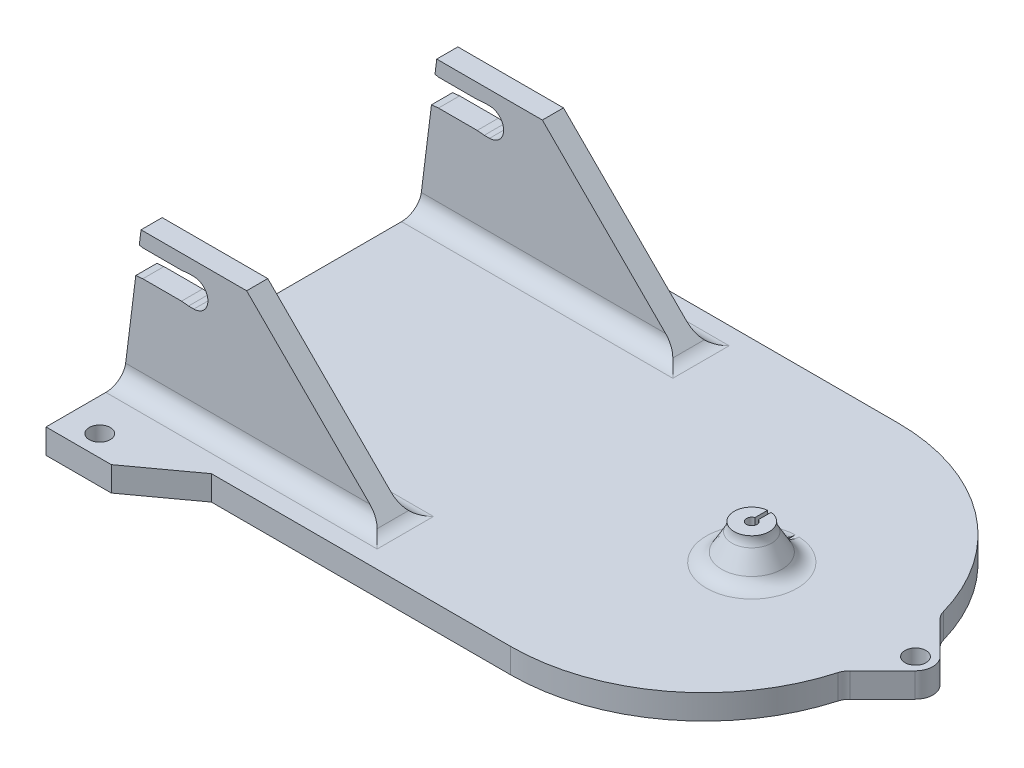
SolidWorks part; units mm, degrees
ref_plane "Front Plane" through (0, 0, 0) normal (0, 0, 1) x (1, 0, 0)
ref_plane "Top Plane" through (0, 0, 0) normal (0, 1, 0) x (1, 0, 0)
ref_plane "Right Plane" through (0, 0, 0) normal (1, 0, 0) x (0, 0, -1)
sketch "Sketch1" plane through (0, 0, 0) normal (0, 1, 0) x (1, 0, 0)
  circle A0 centre (0, 0) radius 55
  dimension "D1" = 110
extrude "Boss-Extrude1" add sketch "Sketch1" along normal blind 7
sketch "Sketch2" plane through (0, 7, 0) normal (0, 1, 0) x (1, 0, 0)
  line L0 (13, 1.4142) -> (13, 4.9749)
  line L1 (14, 1.4142) -> (14, 4.9749)
  line L2 (13, 3.1946) -> (14, 3.1946) construction
  arc A0 (13, 1.4142) -> (14, 1.4142) centre (13.5, 0) ccw
  arc A1 (13, 4.9749) -> (14, 4.9749) centre (13.5, 0) ccw
  circle A2 centre (0, 0) radius 55 construction
  point P10 (13.5, 3.1946)
  dimension "D1" = 3
  dimension "D2" = 10
  dimension "D3" = 13.5
  dimension "D4" = 1
extrude "Boss-Extrude2" add sketch "Sketch2" along normal blind 10
sketch "Sketch3" plane through (0, 7, 0) normal (0, 1, 0) x (1, 0, 0)
  circle A0 centre (0, 0) radius 11
  dimension "D1" = 22
extrude "Cut-Extrude1" [suppressed] cut sketch "Sketch3" against normal through all both
sketch "Sketch4" plane through (0, 7, 0) normal (0, 1, 0) x (1, 0, 0)
  line L0 (0, 55) -> (-120, 55)
  line L1 (-120, 55) -> (-120, -55)
  line L2 (-120, -55) -> (0, -55)
  circle A0 centre (0, 0) radius 55 construction
  arc A1 (0, 55) -> (0, -55) centre (0, 0) ccw
  dimension "D1" = 120
extrude "Boss-Extrude3" add sketch "Sketch4" against normal up to surface (7 mm away) up to face at (0, 0, 55)
sketch "Sketch5" plane through (0, 7, 0) normal (0, 1, 0) x (1, 0, 0)
  line L0 (-120, 0) -> (55, 0) construction
  line L1 (-120, 55) -> (-120, -55) construction
  arc A0 (0, -55) -> (0, 55) centre (0, 0) ccw construction
sketch "Sketch6" plane through (0, 7, 0) normal (0, 1, 0) x (1, 0, 0)
  line L0 (-120, 55) -> (-120, -55) construction
  line L1 (-85, -39) -> (-115, -39)
  line L2 (-85, -39) -> (-85, -45)
  line L3 (-85, -45) -> (-115, -45)
  line L4 (-115, -39) -> (-115, -45)
  line L5 (-120, -55) -> (0, -55) construction
  dimension "D1" = 30
  dimension "D2" = 5
  dimension "D3" = 10
  dimension "D4" = 6
extrude "Boss-Extrude4" add sketch "Sketch6" along normal blind 40
chamfer "Chamfer1" distance 40 angle 45 1 edges at (-85, 7, 42)
sketch "Sketch8" plane through (0, 0, 45) normal (0, 0, 1) x (1, 0, 0)
  line L0 (-115, 47) -> (-120, 7)
  line L1 (-120, 7) -> (55, 7) construction
  line L2 (-120, 7) -> (-115, 7)
  line L3 (-115, 7) -> (-115, 47)
extrude "Boss-Extrude5" add sketch "Sketch8" against normal up to surface (6 mm away) up to face at (-90, 27, 39)
mirror "Mirror1" about plane through (0, 0, 0) normal (0, 0, 1) of "Boss-Extrude4", "Chamfer1", "Boss-Extrude5"
fillet "Fillet1" radius 5 6 edges at (-45, 7, -42) (-45, 7, 42) (-82.5, 7, -45) (-82.5, 7, -39) (-82.5, 7, 39) (-82.5, 7, 45)
chamfer "Chamfer2" distance 5 angle 60 1 edges at (13.5, 7, 5) first distance on face at (13.5, 7, 0.0277)
sketch "Sketch9" plane through (0, 7, 0) normal (0, 1, 0) x (1, 0, 0)
  line L0 (-120, 55) -> (-120, 67)
  line L1 (-120, 67) -> (-101.4622, 67)
  line L2 (-101.4622, 67) -> (-85, 55)
  line L3 (0, 55) -> (-120, 55) construction
  line L4 (-85, 55) -> (-120, 55)
  line L5 (-120, 61) -> (-100.4732, 61) construction
  line L6 (-110.7311, 67) -> (-110.7311, 56.2712) construction
  circle A0 centre (-110.7311, 61) radius 3
  point P14 (-110.2366, 61)
  dimension "D1" = 6
  dimension "D2" = 12
  dimension "D3" = 35
  dimension "D4" = 18.5378
extrude "Boss-Extrude6" add sketch "Sketch9" against normal up to surface (7 mm away) up to face at (-46.25, 0, 0)
mirror "Mirror2" about plane through (0, 0, 0) normal (0, 0, 1) of "Boss-Extrude6"
sketch "Sketch10" plane through (0, 7, 0) normal (0, 1, 0) x (1, 0, 0)
  line L0 (53.2547, 13.7453) -> (67, 0)
  line L1 (67, 0) -> (53.2547, -13.7453)
  circle A0 centre (60, 0) radius 3
  arc A1 (0, -55) -> (0, 55) centre (0, 0) ccw construction
  arc A2 (53.2547, -13.7453) -> (53.2547, 13.7453) centre (0, 0) ccw
  dimension "D1" = 6
  dimension "D2" = 5
  dimension "D3" = 12
extrude "Boss-Extrude7" add sketch "Sketch10" against normal up to surface (7 mm away) up to face at (-69.7406, 0, 0)
fillet "Fillet3" radius 5 3 edges at (53.2547, 3.5, -13.7453) (67, 3.5, 0) (53.2547, 3.5, 13.7453)
fillet "Fillet4" radius 5 2 edges at (13.5, 15.6603, 5) (13.5, 7, 10)
sketch "Sketch11" plane through (0, 0, 45) normal (0, 0, 1) x (1, 0, 0)
  line L0 (-115, 47) -> (-85, 47) construction
  line L1 (-100, 43) -> (-101.5, 43)
  line L2 (-115, 47) -> (-119.375, 12) construction
  line L3 (-100, 35) -> (-101.5, 35)
  line L4 (-115.5, 43) -> (-116.5, 35)
  line L5 (-100, 39) -> (-118.6827, 39) construction
  line L6 (-116.5, 35) -> (-114.5, 35.2)
  line L7 (-114.5, 35.2) -> (-103.5, 35.2)
  line L8 (-103.5, 35.2) -> (-101.5, 35)
  line L9 (-115.5, 43) -> (-114.5, 42.8)
  line L10 (-114.5, 42.8) -> (-103.5, 42.8)
  line L11 (-103.5, 42.8) -> (-101.5, 43)
  arc A1 (-100, 35) -> (-100, 43) centre (-100, 39) ccw
  point P15 (-116, 39)
  dimension "D1" = 8
  dimension "D2" = 20
  dimension "D3" = 8
  dimension "D4" = 2
  dimension "D5" = 2
  dimension "D6" = 11
  dimension "D7" = 0.2
  dimension "D8" = 1.5
  dimension "D9" = 0.2
  dimension "D10" = 1
extrude "Cut-Extrude3" cut sketch "Sketch11" against normal through all both and the other way through all
